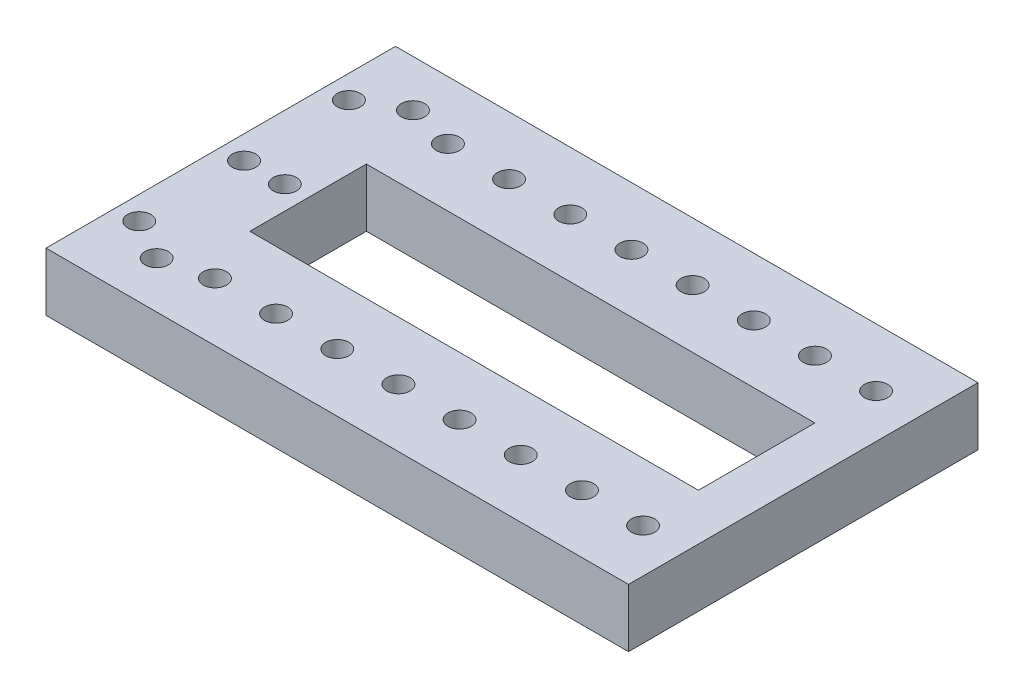
SolidWorks part; units mm, degrees
ref_plane "Front Plane" through (0, 0, 0) normal (0, 0, 1) x (1, 0, 0)
ref_plane "Top Plane" through (0, 0, 0) normal (0, 1, 0) x (1, 0, 0)
ref_plane "Right Plane" through (0, 0, 0) normal (1, 0, 0) x (0, 0, -1)
sketch "Sketch1" plane through (0, 0, 0) normal (0, 1, 0) x (1, 0, 0)
  line L0 (15, 40) -> (15, 20)
  line L1 (0, 0) -> (100, 0)
  line L2 (0, 0) -> (0, 60)
  line L3 (0, 60) -> (100, 60)
  line L4 (100, 0) -> (100, 60)
  line L5 (15, 20) -> (92, 20)
  line L6 (92, 20) -> (92, 40)
  line L7 (92, 40) -> (15, 40)
  circle A0 centre (4, 48) radius 2
  circle A1 centre (11, 52) radius 2
  circle A2 centre (4, 30) radius 2
  circle A3 centre (11, 30) radius 2
  circle A4 centre (4, 12) radius 2
  circle A5 centre (11, 8) radius 2
  circle A6 centre (19, 10) radius 2
  circle A7 centre (19, 50) radius 2
  circle A8 centre (29.5, 50) radius 2
  circle A9 centre (29.5, 10) radius 2
  circle A10 centre (40, 50) radius 2
  circle A11 centre (40, 10) radius 2
  circle A12 centre (50.5, 50) radius 2
  circle A13 centre (50.5, 10) radius 2
  circle A14 centre (61, 50) radius 2
  circle A15 centre (61, 10) radius 2
  circle A16 centre (71.5, 50) radius 2
  circle A17 centre (71.5, 10) radius 2
  circle A18 centre (82, 50) radius 2
  circle A19 centre (82, 10) radius 2
  circle A20 centre (92.5, 50) radius 2
  circle A21 centre (92.5, 10) radius 2
  point P26 (0, 0)
  point P54 (0, 0)
  dimension "D4" = 4
  dimension "D5" = 4
  dimension "D6" = 4
  dimension "D7" = 4
  dimension "D8" = 4
  dimension "D9" = 4
  dimension "D25" = 4
  dimension "D26" = 4
  dimension "D1" = 60
  dimension "D2" = 100
  dimension "D3" = 15
  dimension "D10" = 8
  dimension "D11" = 4
  dimension "D12" = 4
  dimension "D13" = 12
  dimension "D14" = 4
  dimension "D15" = 30
  dimension "D16" = 30
  dimension "D17" = 4
  dimension "D18" = 4
  dimension "D19" = 12
  dimension "D20" = 8
  dimension "D21" = 4
  dimension "D22" = 20
  dimension "D23" = 20
  dimension "D24" = 8
  dimension "D27" = 10
  dimension "D28" = 10
  dimension "D29" = 4
  dimension "D30" = 4
  dimension "D31" = 8
extrude "Boss-Extrude1" add sketch "Sketch1" along normal blind 10
